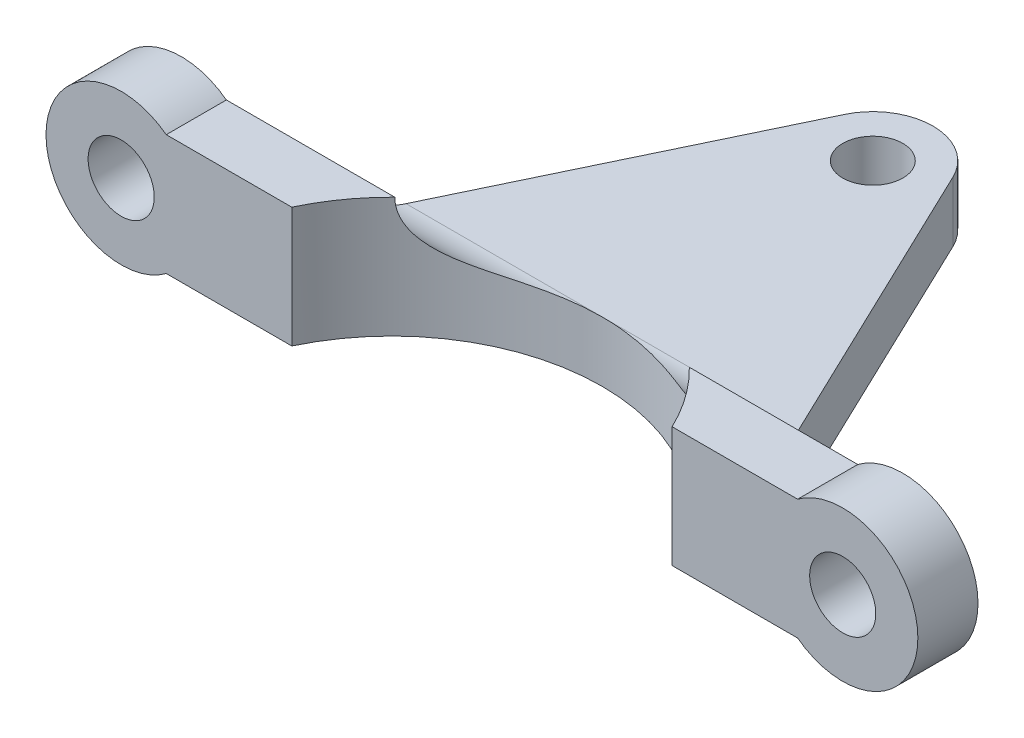
SolidWorks part; units mm, degrees
ref_plane "Front Plane" through (0, 0, 0) normal (0, 0, 1) x (1, 0, 0)
ref_plane "Top Plane" through (0, 0, 0) normal (0, 1, 0) x (1, 0, 0)
ref_plane "Right Plane" through (0, 0, 0) normal (1, 0, 0) x (0, 0, -1)
sketch "Sketch1" plane through (0, 0, 0) normal (0, 1, 0) x (1, 0, 0)
  line L0 (0, 0) -> (-12, 0) construction
  line L1 (-12, 0) -> (12, 0) construction
  line L2 (-21.3034, 3) -> (20.0845, 3) construction
  line L3 (-12, 0) -> (-12, 3) construction
  line L4 (12, 0) -> (12, 3) construction
  line L5 (-8.4853, 3) -> (-14, 3)
  line L6 (-14, 3) -> (-14, 5)
  line L7 (-14, 5) -> (14, 5)
  line L8 (14, 5) -> (14, 3)
  line L9 (14, 3) -> (8.4853, 3)
  line L10 (-7.4833, 5) -> (-1.8039, 16.8636)
  line L11 (7.4833, 5) -> (1.8039, 16.8636)
  line L12 (-8.4853, 3) -> (8.4853, 3)
  circle A0 centre (0, 0) radius 7
  circle A1 centre (0, 16) radius 1
  circle A2 centre (0, 0) radius 9
  circle A3 centre (0, 16) radius 2
  dimension "D1" = 14
  dimension "D3" = 2
  dimension "D4" = 18
  dimension "D11" = 4
  dimension "D2" = 16
  dimension "D5" = 12
  dimension "D6" = 12
  dimension "D7" = 3
  dimension "D8" = 2
  dimension "D9" = 2
  dimension "D10" = 2
extrude "Boss-Extrude1" add sketch "Sketch1" along normal blind 4 contours A2 L7 L6 L5 | L7 A2 L12 A0 | L7 A2 A0 | A3 L10 A2 L11 | A2 L9 L8 L7 | L12 A2 L7 A0 | A3 A1 region at (-6.8506, 0, -4.0295) region at (-11.0112, 0, -4.0279) region at (0, 0, -7.0236) region at (0, 0, -10.98) region at (6.8506, 0, -4.0295) region at (0, 0, -17.9434) region at (11.0112, 0, -4.0279)
sketch "Sketch2" plane through (0, 0, -5) normal (0, 0, -1) x (-1, 0, 0)
  line L0 (14, 4) -> (7.4833, 4) construction
  line L1 (14, 4) -> (14, 0) construction
  line L2 (-7.4833, 4) -> (-14, 4) construction
  line L3 (-14, 4) -> (-14, 0) construction
  circle A0 centre (-12, 2) radius 1.1
  circle A1 centre (12, 2) radius 1.1
  dimension "D1" = 2.2
  dimension "D2" = 2.2
  dimension "D3" = 2
  dimension "D4" = 2
  dimension "D5" = 2
  dimension "D6" = 2
extrude "Cut-Extrude1" cut sketch "Sketch2" against normal up to surface (2 mm away) up to face at (10.1623, 2, -3)
sketch "Sketch3" plane through (0, 0, -5) normal (0, 0, -1) x (-1, 0, 0)
  line L0 (7.4833, 4) -> (7.4833, 0) construction
  line L1 (-7.4833, 4) -> (7.4833, 4)
  line L2 (-7.4833, 4) -> (-7.4833, 2)
  line L3 (-7.4833, 2) -> (7.4833, 2)
  line L4 (7.4833, 4) -> (7.4833, 2)
extrude "Cut-Extrude2" cut sketch "Sketch3" along normal blind 23
fillet "Fillet1" radius 3 2 edges at (7.4833, 1, -5) (-7.4833, 1, -5)
fillet "Fillet2" radius 2 4 edges at (-14, 0, -4) (-14, 4, -4) (14, 0, -4) (14, 4, -4)
fillet "Fillet3" radius 2 2 edges at (7.1361, 2, -5) (-7.1361, 2, -5)
sketch "Sketch4" plane through (0, 0, -5) normal (0, 0, -1) x (-1, 0, 0)
  circle A0 centre (12, 2) radius 1.1
  circle A1 centre (12, 2) radius 2.5
  circle A2 centre (-12, 2) radius 1.1
  circle A3 centre (-12, 2) radius 2.5
  dimension "D1" = 5
  dimension "D2" = 5
extrude "Boss-Extrude2" add sketch "Sketch4" against normal up to surface (2 mm away) up to face at (10.9, 2, -3)
